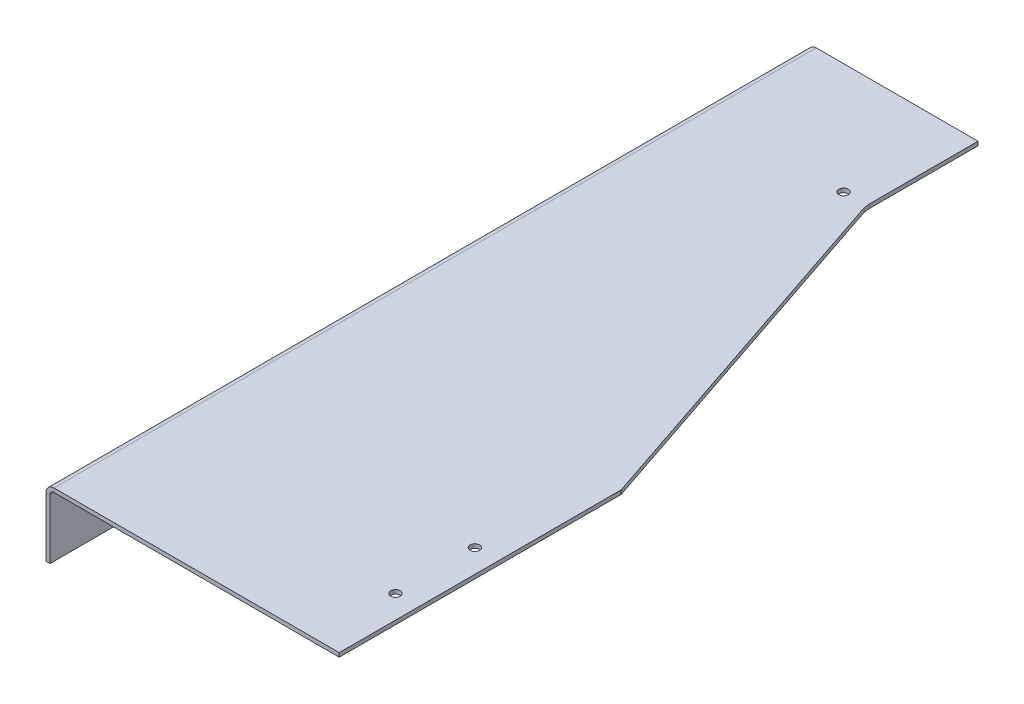
SolidWorks part; units mm, degrees
note: The reader was unsure of these and kept them because the rebuilt part matched: flange length of "Edge-Flange1".
material "6061 Alloy"
ref_plane "Front Plane" through (0, 0, 0) normal (0, 0, 1) x (1, 0, 0)
ref_plane "Top Plane" through (0, 0, 0) normal (0, 1, 0) x (1, 0, 0)
ref_plane "Right Plane" through (0, 0, 0) normal (1, 0, 0) x (0, 0, -1)
sketch "Sketch1" plane through (0, 0, 0) normal (0, 1, 0) x (1, 0, 0)
  line L0 (0, 304.8) -> (76.2, 304.8)
  line L1 (76.2, 304.8) -> (152.4, 0)
  line L2 (152.4, 0) -> (0, 0)
  line L3 (0, 0) -> (0, 304.8)
  dimension "D1" = 76.2
  dimension "D2" = 304.8
  dimension "D3" = 152.4
base flange "Base-Flange1" sketch "Sketch1" thickness 1.5875 reverse thickness direction no parameters "D1"=254
edge flange "Edge-Flange1" sketch "Sketch8" flange angle 90 flange length 25.4 flange position material inside bend radius 1.6002 thickness 1.5875 relief rectangular parameters "D6"=10
sketch "Sketch8" plane through (0, -1.5875, 0) normal (1, 0, 0) x (0, 0, 1)
  line L2 (-304.8, 0) -> (-304.8, 25.4)
  line L3 (-304.8, 25.4) -> (0, 25.4)
  line L4 (0, 25.4) -> (0, 0)
  line L14 (0, 0) -> (-304.8, 0) construction
  line L15 (0, 0) -> (-304.8, 0)
bend "EdgeBend1" bend radius 1.6002 bend angle 90 parameters "D5"=1
sketch "Sketch9" plane through (0, -1.5875, 0) normal (0, -1, 0) x (-1, 0, 0)
  line L0 (-67.8559, 304.8) -> (-67.8559, 261.2273)
  line L1 (-76.2, 304.8) -> (-3.1877, 304.8) construction
  line L2 (-67.8559, 261.2273) -> (-68.1839, 258.8678)
  line L3 (-68.1839, 258.8678) -> (-116.938, 113.6264)
  line L4 (-116.938, 113.6264) -> (-117.2408, 112.7243)
  line L5 (-117.2408, 112.7243) -> (-117.2408, 0)
extrude "Cut-Extrude1" cut sketch "Sketch9" against normal through all and the other way through all flip side to cut contours L0 L2 L3 L4 L5 normal cut yes
hole_wizard "#6 Clearance Hole1" positions "Sketch12" profile "Sketch10" hole size "#6" standard "ANSI Inch" end condition through all
sketch "Sketch12" plane through (0, 0, 0) normal (0, 1, 0) x (1, 0, 0)
  point P0 (58.5644, 260.35)
sketch "Sketch10" plane through (58.5644, 0, -260.35) normal (1, 0, 0) x (0, 0, 1)
  line L0 (0, 0) -> (0, 26.9875)
  line L1 (0, 26.9875) -> (1.8986, 26.9875)
  line L2 (1.8986, 26.9875) -> (1.8986, 0)
  line L5 (1.8986, 0) -> (0, 0)
  line L11 (0, -6.35) -> (0, 107.95) construction
  dimension "Thru Hole Dia." = 3.7973
  dimension "Thru Hole Depth" = 26.9875
hole_wizard "#6 Clearance Hole2" positions "Sketch14" profile "Sketch13" hole size "#6" standard "ANSI Inch" end condition through all
sketch "Sketch14" plane through (0, 0, 0) normal (0, 1, 0) x (1, 0, 0)
  point P0 (107.9896, 31.75)
  point P3 (107.9896, 63.5)
sketch "Sketch13" plane through (107.9896, 0, -31.75) normal (1, 0, 0) x (0, 0, 1)
  line L0 (0, 0) -> (0, 26.9875)
  line L1 (0, 26.9875) -> (1.8986, 26.9875)
  line L2 (1.8986, 26.9875) -> (1.8986, 0)
  line L5 (1.8986, 0) -> (0, 0)
  line L11 (0, -6.35) -> (0, 107.95) construction
  dimension "Thru Hole Dia." = 3.7973
  dimension "Thru Hole Depth" = 26.9875
sketch "Bend-Lines1" [suppressed] plane through (0, 0, 0) normal (0, 1, 0) x (1, 0, 0)
sketch "Bounding-Box1" [suppressed] plane through (0, 0, 0) normal (0, 1, 0) x (1, 0, 0)
sheet metal parameters "Sheet-Metal1" thickness 1.5875 parameters "D1"=254
flat pattern "Flat-Pattern1" [suppressed]
sketch "Bend-Lines2" plane through (0, 0, 0) normal (0, 1, 0) x (1, 0, 0)
sketch3d "Bounding-Box2" [suppressed]
  line L0 (0, 0, 0) -> (0, 304.8, 0) construction
  line L1 (-152.4, 0, 0) -> (-152.4, 304.8, 0) construction
  line L2 (0, 0, 0) -> (-152.4, 0, 0) construction
  line L3 (0, 304.8, 0) -> (-152.4, 304.8, 0) construction
sheet metal parameters "Sheet-Metal2" thickness 1.5875 parameters "D1"=254
flat pattern "Flat-Pattern1"
sketch "Bend-Lines2" plane through (0, 0, 0) normal (0, 1, 0) x (1, 0, 0)
  line L0 (1.3075, 304.8) -> (1.3075, 0) construction
  line L1 (1.3075, 304.8) -> (1.3075, 0) construction
sketch3d "Bounding-Box2" [suppressed]
  line L0 (-24.3725, 0, 0) -> (-24.3725, 304.8, 0) construction
  line L1 (152.4, 0, 0) -> (152.4, 304.8, 0) construction
  line L2 (-24.3725, 0, 0) -> (152.4, 0, 0) construction
  line L3 (-24.3725, 304.8, 0) -> (152.4, 304.8, 0) construction
bend of the flat pattern "Flatten-<EdgeBend1>1"
sheet metal parameters "Sheet-Metal3" thickness 1.5875 parameters "D1"=254
flat pattern "Flat-Pattern1"
sketch "Bend-Lines2" plane through (0, 0, 0) normal (0, 1, 0) x (1, 0, 0)
  line L0 (1.3075, 304.8) -> (1.3075, 0) construction
  line L1 (1.3075, 304.8) -> (1.3075, 0) construction
sketch3d "Bounding-Box2" [suppressed]
  line L0 (-24.3725, 0, 0) -> (-24.3725, 304.8, 0) construction
  line L1 (117.2408, 0, 0) -> (117.2408, 304.8, 0) construction
  line L2 (-24.3725, 0, 0) -> (117.2408, 0, 0) construction
  line L3 (-24.3725, 304.8, 0) -> (117.2408, 304.8, 0) construction
bend of the flat pattern "Flatten-<EdgeBend1>1"
sheet metal parameters "Sheet-Metal4" thickness 1.5875 parameters "D1"=254
flat pattern "Flat-Pattern1"
sketch "Bend-Lines2" plane through (0, 0, 0) normal (0, 1, 0) x (1, 0, 0)
  line L0 (1.3075, 304.8) -> (1.3075, 0) construction
  line L1 (1.3075, 304.8) -> (1.3075, 0) construction
sketch3d "Bounding-Box2" [suppressed]
  line L0 (-24.3725, 0, 0) -> (-24.3725, 304.8, 0) construction
  line L1 (117.2408, 0, 0) -> (117.2408, 304.8, 0) construction
  line L2 (-24.3725, 0, 0) -> (117.2408, 0, 0) construction
  line L3 (-24.3725, 304.8, 0) -> (117.2408, 304.8, 0) construction
bend of the flat pattern "Flatten-<EdgeBend1>1"
sheet metal parameters "Sheet-Metal6" thickness 1.5875 parameters "D1"=254
flat pattern "Flat-Pattern1"
sketch "Bend-Lines2" plane through (0, 0, 0) normal (0, 1, 0) x (1, 0, 0)
  line L0 (1.3075, 304.8) -> (1.3075, 0) construction
  line L1 (1.3075, 304.8) -> (1.3075, 0) construction
sketch3d "Bounding-Box2" [suppressed]
  line L0 (-24.3725, 0, 0) -> (-24.3725, 304.8, 0) construction
  line L1 (117.2408, 0, 0) -> (117.2408, 304.8, 0) construction
  line L2 (-24.3725, 0, 0) -> (117.2408, 0, 0) construction
  line L3 (-24.3725, 304.8, 0) -> (117.2408, 304.8, 0) construction
bend of the flat pattern "Flatten-<EdgeBend1>1"
